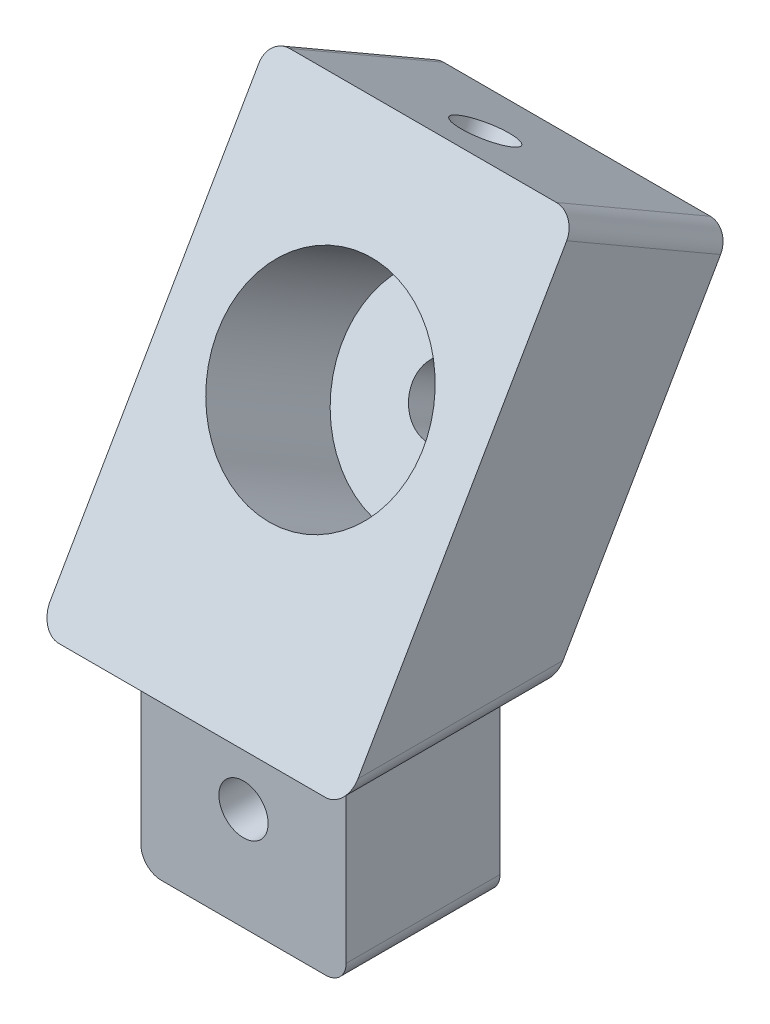
SolidWorks part; units mm, degrees
note: '?' marks a value the reader was unsure of.
ref_plane "Front Plane" through (0, 0, 0) normal (0, 0, 1) x (1, 0, 0)
ref_plane "Top Plane" through (0, 0, 0) normal (0, 1, 0) x (1, 0, 0)
ref_plane "Right Plane" through (0, 0, 0) normal (1, 0, 0) x (0, 0, -1)
sketch "Sketch1" plane through (0, 0, 0) normal (0, 0, 1) x (1, 0, 0)
  line L1 (-5, -5) -> (5, -5)
  line L2 (-5, -5) -> (-5, 5)
  line L3 (-5, 5) -> (5, 5)
  line L4 (5, -5) -> (5, 5)
  line L5 (-5, -5) -> (5, 5) construction
  line L6 (-5, 5) -> (5, -5) construction
  point P0 (0, 0)
  dimension "D1" = 10
  dimension "D2" = 10
extrude "Boss-Extrude1" add sketch "Sketch1" along normal mid plane 7.5
sketch "Sketch2" plane through (0, 0, -3.75) normal (0, 0, -1) x (-1, 0, 0)
  line L1 (-3.25, -3.25) -> (3.25, -3.25)
  line L2 (-3.25, -3.25) -> (-3.25, 3.25)
  line L3 (-3.25, 3.25) -> (3.25, 3.25)
  line L4 (3.25, -3.25) -> (3.25, 3.25)
  line L5 (-3.25, -3.25) -> (3.25, 3.25) construction
  line L6 (-3.25, 3.25) -> (3.25, -3.25) construction
  line L7 (0, 4.125) -> (0, -4.125) construction
  line L10 (-5, 5) -> (5, 5) construction
  point P0 (0, 0)
  dimension "D1" = 6.5
  dimension "D2" = 6.5
  dimension "D3" = 1.75
extrude "Cut-Extrude1" cut sketch "Sketch2" against normal blind 5
sketch "Sketch3" plane through (0, 0, 0) normal (1, 0, 0) x (0, 0, -1)
  line L0 (-6.25, 5) -> (5, 24.4856)
  line L1 (5, 24.4856) -> (12.5, 20.1554)
  line L2 (12.5, 20.1554) -> (3.75, 5)
  line L3 (3.75, 5) -> (-6.25, 5)
  dimension "D1" = 17.5
  dimension "D2" = 60
  dimension "D3" = 10
extrude "Boss-Extrude2" add sketch "Sketch3" along normal mid plane 15
sketch "Sketch5" plane through (0, -0.3738, -0.6474) normal (0, -0.5, -0.866) x (-1, 0, 0)
  line L0 (0, 4.125) -> (0, -4.125) construction
  line L1 (-7.5, 23.7051) -> (7.5, 23.7051) construction
  circle A0 centre (0, 13.7051) radius 1.5875
  point P0 (0, 13.7051)
  dimension "D2" = 3.175
  dimension "D1" = 10
hole_wizard "3/8 Clearance Hole1" [suppressed] positions "Sketch6" profile "Sketch7" hole size "3/8" standard "ANSI Inch"
sketch "Sketch6" [suppressed] plane through (0, -0.4575, -0.7925) normal (0, -0.5, -0.866) x (-1, 0, 0)
  point P0 (0, 10.9151)
sketch "Sketch7" [suppressed] plane through (0, 8.9952, -6.25) normal (1, 0, 0) x (0, 0.866, -0.5)
  line L0 (0, 0) -> (0, 14.6142)
  line L1 (0, 14.6142) -> (5.0419, 14.6142)
  line L2 (5.0419, 14.6142) -> (5.0419, 0)
  line L5 (5.0419, 0) -> (0, 0)
  line L11 (0, -6.35) -> (0, 107.95) construction
  dimension "Thru Hole Dia." = 10.0838
  dimension "Thru Hole Depth" = 14.6142
sketch "Sketch8" plane through (0, 0, 3.75) normal (0, 0, 1) x (1, 0, 0)
  line L0 (0, -4.125) -> (0, 4.125) construction
  line L1 (-5, -5) -> (5, -5) construction
  point P0 (0, 0)
  dimension "D1" = 5
hole_wizard "M2 Clearance Hole1" positions "Sketch9" profile "Sketch11" hole size "M2" standard "ANSI Metric" end condition through all
sketch "Sketch9" plane through (0, 0, 3.75) normal (0, 0, 1) x (1, 0, 0)
  point P0 (0, 0)
sketch "Sketch11" plane through (0, 0, 3.75) normal (1, 0, 0) x (0, -1, 0)
  line L0 (0, 0) -> (0, 16.25)
  line L1 (0, 16.25) -> (1.2, 16.25)
  line L2 (1.2, 16.25) -> (1.2, 0)
  line L5 (1.2, 0) -> (0, 0)
  line L11 (0, -6.35) -> (0, 107.95) construction
  dimension "Thru Hole Dia." = 2.4
  dimension "Thru Hole Depth" = 16.25
fillet "Fillet5" radius 1 4 edges at (7.5, 5, 1.25) (7.5, 22.3205, -8.75) (-7.5, 5, 1.25) (-7.5, 22.3205, -8.75)
fillet "Fillet1" radius 1 2 edges at (5, 5, 0) (-5, 5, 0)
fillet "Fillet2" [suppressed] radius 2
fillet "Fillet3" radius 1 2 edges at (5, -5, 0) (-5, -5, 0)
ref_axis "Axis1" through (0, 11.4952, -7.5) along (0, 0.5, 0.866)?
sketch "Sketch17" plane through (0, 3.9563, 6.8526) normal (0, 0.5, 0.866) x (1, 0, 0)
  circle A0 centre (0, 13.7051) radius 5
  point P0 (0, 13.7051)
  dimension "D1" = 10
extrude "Cut-Extrude2" cut sketch "Sketch17" against normal blind 7
extrude "Cut-Extrude3" cut sketch "Sketch5" against normal blind 5 contours A0
sketch "Sketch18" plane through (0, 20.5292, -11.8526) normal (0, 0.866, -0.5) x (1, 0, 0)
  line L0 (0, -10.3125) -> (0, 10.3125) construction
  line L1 (6.5, -7.9127) -> (-6.5, -7.9127) construction
  circle A0 centre (0, -4.4127) radius 1.35
  point P0 (0, -4.4127)
  dimension "D2" = 2.7
  dimension "D1" = 3.5
fillet "Fillet4" radius 1 1 edges at (0, 5, 3.75)
extrude "Cut-Extrude4" cut sketch "Sketch18" against normal up to next contours A0
